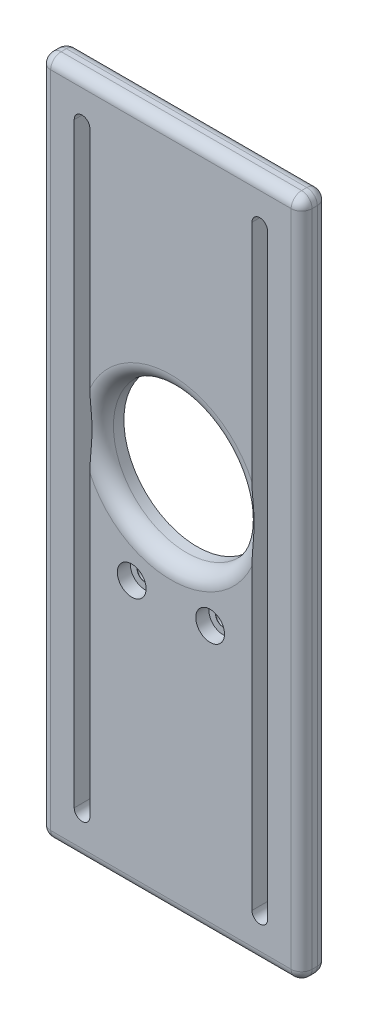
SolidWorks part; units mm, degrees
ref_plane "Front Plane" through (0, 0, 0) normal (0, 0, 1) x (1, 0, 0)
ref_plane "Top Plane" through (0, 0, 0) normal (0, 1, 0) x (1, 0, 0)
ref_plane "Right Plane" through (0, 0, 0) normal (1, 0, 0) x (0, 0, -1)
sketch "Base" plane through (0, 0, 0) normal (0, 0, 1) x (1, 0, 0)
  line L0 (43.6224, 52.8458) -> (43.6224, 40.7373) construction
  line L1 (3.1224, 117.8458) -> (53.1224, 117.8458)
  line L2 (3.1224, 117.8458) -> (3.1224, -12.1542)
  line L3 (3.1224, -12.1542) -> (53.1224, -12.1542)
  line L4 (53.1224, 117.8458) -> (53.1224, -12.1542)
  line L8 (45.1224, 109.8458) -> (45.1224, -4.1542) construction
  line L9 (3.1224, 40.7373) -> (3.1224, 52.8458) construction
  line L12 (46.6224, 109.8458) -> (46.6224, -4.1542)
  line L13 (43.6224, 109.8458) -> (43.6224, -4.1542)
  line L14 (11.1224, 109.8458) -> (11.1224, -4.1542) construction
  line L15 (12.6224, 109.8458) -> (12.6224, -4.1542)
  line L16 (9.6224, 109.8458) -> (9.6224, -4.1542)
  circle A4 centre (28.1224, 59.8458) radius 14
  arc A5 (46.6224, 109.8458) -> (43.6224, 109.8458) centre (45.1224, 109.8458) ccw
  arc A6 (43.6224, -4.1542) -> (46.6224, -4.1542) centre (45.1224, -4.1542) ccw
  arc A7 (12.6224, 109.8458) -> (9.6224, 109.8458) centre (11.1224, 109.8458) ccw
  arc A8 (9.6224, -4.1542) -> (12.6224, -4.1542) centre (11.1224, -4.1542) ccw
  point P6 (28.1224, 117.8458)
  point P13 (45.1224, 52.8458)
  point P31 (11.1224, 52.8458)
  dimension "D5" = 28
  dimension "D6" = 17
  dimension "D4" = 8
  dimension "D11" = 114
  dimension "D2" = 8
  dimension "D7" = 130
  dimension "D8" = 50
  dimension "D9" = 17
  dimension "D10" = 50
  dimension "D12" = 3
extrude "Boss-Extrude1" add sketch "Base" along normal blind 5
sketch "Sketch4" plane through (0, 0, 5) normal (0, 0, 1) x (1, 0, 0)
  line L0 (28.1224, 45.8458) -> (53.1224, 45.8458) construction
  line L1 (53.1224, -12.1542) -> (53.1224, 117.8458) construction
  line L2 (53.1224, 45.8458) -> (53.1224, 32.1458) construction
  line L3 (53.1224, 32.1458) -> (3.1224, 32.1458) construction
  line L4 (3.1224, 117.8458) -> (3.1224, -12.1542) construction
  line L5 (3.1224, 32.1458) -> (3.1224, 45.8458) construction
  line L6 (3.1224, 45.8458) -> (28.1224, 45.8458) construction
  line L7 (3.1224, 38.9958) -> (20.6224, 38.9958) construction
  line L8 (53.1224, 38.9958) -> (35.6224, 38.9958) construction
  circle A0 centre (28.1224, 59.8458) radius 14 construction
  dimension "D1" = 17.5
  dimension "D2" = 15
  dimension "D3" = 13.7
hole_wizard "CBORE for M2.5 SHCS1" positions "3DSketch1" profile "Sketch5" counterbore size "M2.5" standard "ANSI Metric" end condition through all
sketch3d "3DSketch1"
  point P0 (20.6224, 38.9958, 5)
  point P3 (35.6224, 38.9958, 5)
sketch "Sketch5" plane through (20.6224, 38.9958, 5) normal (1, 0, 0) x (0, -1, 0)
  line L0 (0, 0) -> (0, 5)
  line L1 (0, 5) -> (1.45, 5)
  line L2 (1.45, 2.525) -> (1.45, 5)
  line L3 (1.45, 2.525) -> (1.475, 2.5)
  line L4 (1.475, 2.5) -> (2.75, 2.5)
  line L5 (2.75, 2.5) -> (2.75, 0)
  line L7 (0, 0) -> (2.75, 0)
  line L9 (-1.45, 2.525) -> (-1.475, 2.5) construction
  line L11 (0, -6.35) -> (0, 107.95) construction
  dimension "Thru Hole Dia." = 2.9
  dimension "Thru Hole Depth" = 5
  dimension "C'Bore Dia." = 5.5
  dimension "C'Bore Depth" = 2.5
  dimension "Mid C'Sink Dia." = 2.95
  dimension "Mid C'Sink Angle" = 90
fillet "Fillet3" radius 2 12 edges at (28.1224, -12.1542, 5) (28.1224, -12.1542, 0) (28.1224, 117.8458, 5) (28.1224, 117.8458, 0) (3.1224, 117.8458, 2.5) (3.1224, 52.8458, 5) (3.1224, -12.1542, 2.5) (3.1224, 52.8458, 0) (53.1224, -12.1542, 2.5) (53.1224, 52.8458, 5) (53.1224, 117.8458, 2.5) (53.1224, 52.8458, 0)
fillet "Fillet5" radius 3 1 edges at (42.1224, 59.8458, 5)
